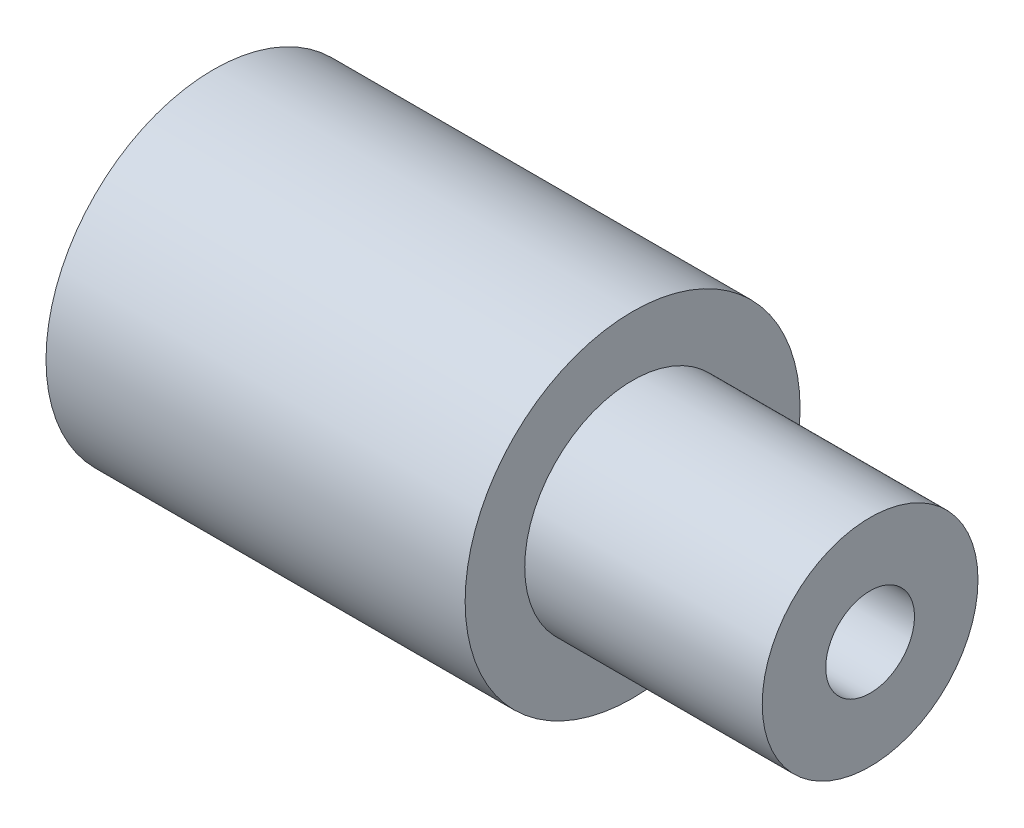
SolidWorks part; units mm, degrees
ref_plane "Front Plane" through (0, 0, 0) normal (0, 0, 1) x (1, 0, 0)
ref_plane "Top Plane" through (0, 0, 0) normal (0, 1, 0) x (1, 0, 0)
ref_plane "Right Plane" through (0, 0, 0) normal (1, 0, 0) x (0, 0, -1)
sketch "Reducer_T8_T4 Sketch" plane through (0, 0, 0) normal (0, 0, 1) x (1, 0, 0)
  line L0 (-1000, 0) -> (1000, 0) construction
  line L1 (-23.5, 0) -> (-23.5, 11.988)
  line L2 (-23.5, 11.988) -> (0.5, 11.988)
  line L3 (0.5, 11.988) -> (6.5, 11.988)
  line L4 (6.5, 11.988) -> (6.5, 7.722)
  line L5 (6.5, 7.722) -> (23.5, 7.722)
  line L6 (23.5, 7.722) -> (23.5, 0)
  line L7 (23.5, 0) -> (-23.5, 0)
revolve "Reducer_T8_T4" add sketch "Reducer_T8_T4 Sketch" angle 360 about L0
ref_axis "Engine Axis" through (25.85, 0, 0) along (-1, 0, 0)
sketch "Socket 1 Sketch" plane through (0, 0, 0) normal (0, 0, 1) x (1, 0, 0)
  line L0 (-1000, 0) -> (1000, 0) construction
  line L1 (-24.5, 0) -> (-24.5, 6.35)
  line L2 (-24.5, 6.35) -> (-0.6, 6.35)
  line L3 (-0.6, 6.35) -> (-0.6, 0)
  line L4 (-0.6, 0) -> (-24.5, 0)
revolve "Socket 1" cut sketch "Socket 1 Sketch" angle 360 about L0
sketch "Socket 2 Sketch" plane through (0, 0, 0) normal (0, 0, 1) x (1, 0, 0)
  line L0 (-1000, 0) -> (1000, 0) construction
  line L1 (8.3, 0) -> (8.3, 3.175)
  line L2 (8.3, 3.175) -> (24.5, 3.175)
  line L3 (24.5, 3.175) -> (24.5, 0)
  line L4 (24.5, 0) -> (8.3, 0)
revolve "Socket 2" cut sketch "Socket 2 Sketch" angle 360 about L0
